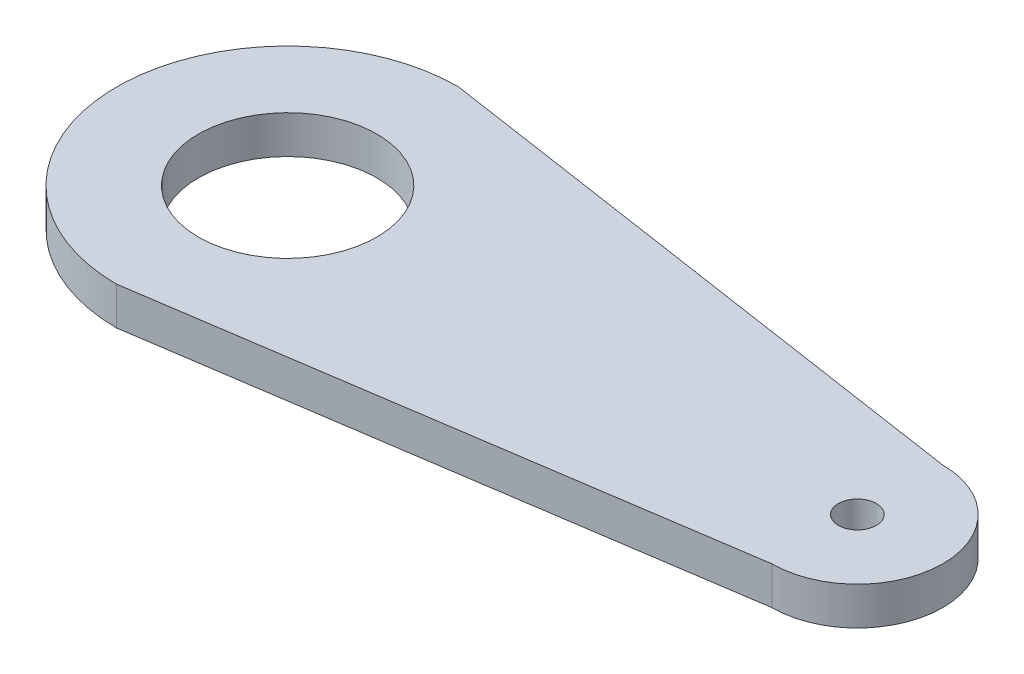
SolidWorks part; units mm, degrees
ref_plane "Front Plane" through (0, 0, 0) normal (0, 0, 1) x (1, 0, 0)
ref_plane "Top Plane" through (0, 0, 0) normal (0, 1, 0) x (1, 0, 0)
ref_plane "Right Plane" through (0, 0, 0) normal (1, 0, 0) x (0, 0, -1)
sketch "Sketch1" plane through (0, 0, 0) normal (0, 1, 0) x (1, 0, 0)
  line L0 (0, 0) -> (15, 0) construction
  line L1 (0, 4.5) -> (15, 2.25)
  line L2 (0, -4.5) -> (15, -2.25)
  circle A0 centre (0, 0) radius 2.35
  arc A1 (1.3203, 4.302) -> (1.3203, -4.302) centre (0, 0) ccw
  arc A2 (15, -2.25) -> (15, 2.25) centre (15, 0) ccw
  circle A3 centre (15, 0) radius 0.5
  dimension "D1" = 4.7
  dimension "D2" = 15
  dimension "D3" = 4.5
  dimension "D4" = 1
  dimension "D5" = 4.5
extrude "Boss-Extrude1" add sketch "Sketch1" along normal blind 1 contours L2 A2 L1 A1 A0 region at (5.9356, 0, 0)
